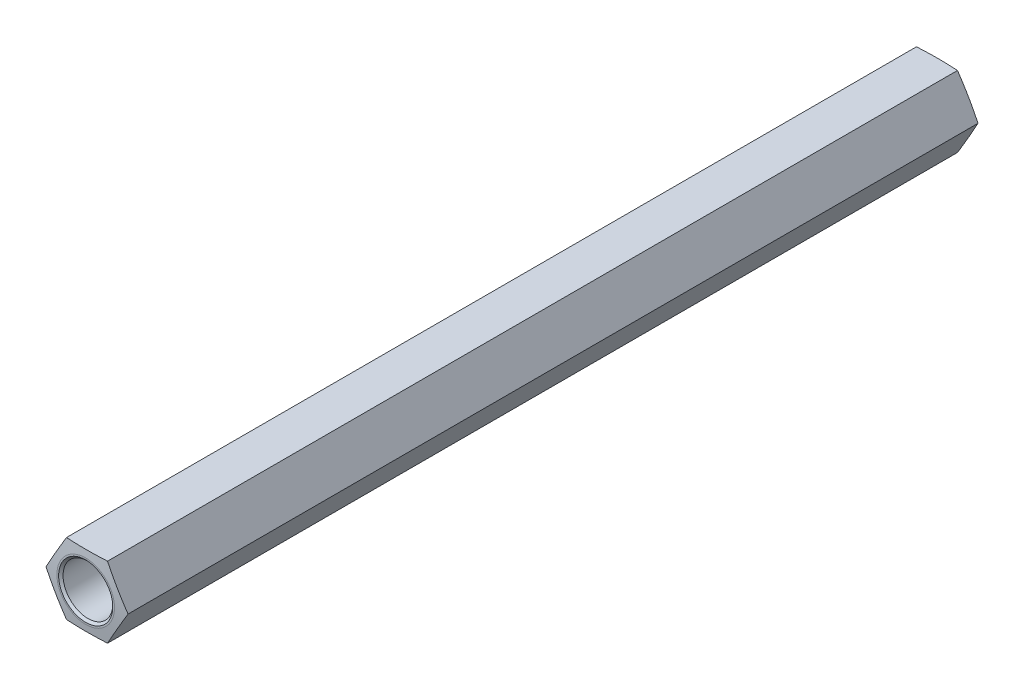
SolidWorks part; units mm, degrees
material "Plain Carbon Steel"
ref_plane "Front Plane" through (0, 0, 0) normal (0, 0, 1) x (1, 0, 0)
ref_plane "Top Plane" through (0, 0, 0) normal (0, 1, 0) x (1, 0, 0)
ref_plane "Right Plane" through (0, 0, 0) normal (1, 0, 0) x (0, 0, -1)
sketch "Sketch1" plane through (0, 0, 0) normal (0, 0, 1) x (1, 0, 0)
  line L0 (-3.6662, 0) -> (-1.8331, -3.175)
  line L1 (-1.8331, -3.175) -> (1.8331, -3.175)
  line L2 (1.8331, -3.175) -> (3.6662, 0)
  line L3 (3.6662, 0) -> (1.8331, 3.175)
  line L4 (1.8331, 3.175) -> (-1.8331, 3.175)
  line L5 (-1.8331, 3.175) -> (-3.6662, 0)
  line L6 (0, 3.175) -> (0, -3.175) construction
  line L7 (-2.7496, 1.5875) -> (0, 0) construction
  circle A0 centre (0, 0) radius 2.22
  point P2 (0, 0)
  dimension "D8" = 4.44
  dimension "D1" = 3.6662
  dimension "D2" = 3.6662
  dimension "D3" = 3.6662
  dimension "D4" = 3.175
  dimension "D5" = 6.35
  dimension "D6" = 7.3323
  dimension "D7" = 3.6662
extrude "Extrude1" add sketch "Sketch1" along normal mid plane 76.2
cosmetic thread "Cosmetic Thread1" parameters "D2"=5
chamfer "Chamfer1" distance 0.2 angle 45 2 edges at (2.22, 0, -38.1) (2.22, 0, 38.1)
ref_plane "Plane1" through (0, 0, 0) normal (0, 1, 0) x (-1, 0, 0)
sketch "Sketch2" plane through (0, 0, 0) normal (0, -1, 0) x (1, 0, 0)
  line L0 (-2.5727, -38.1) -> (-3.6662, -37.98)
  line L3 (-3.6662, -37.98) -> (-3.6662, -38.1)
  line L4 (-3.6662, -38.1) -> (-2.5727, -38.1)
  dimension "D1" = 1.0934
  dimension "D2" = 0.12
revolve "Cut-Revolve1" cut sketch "Sketch2" angle 360 about axis through (0, 0, 38.1) along (0, 0, -1)
mirror "Mirror1" about plane through (0, 0, 0) normal (0, 0, 1) of "Cut-Revolve1"
ref_axis "Axis1" through (0, 0, -43.064) along (0, 0, 1)
ref_plane "Plane2" through (0, 0, -39.39) normal (0, 0, 1) x (1, 0, 0)
ref_plane "Plane3" through (0, 0, 39.39) normal (0, 0, 1) x (1, 0, 0)
